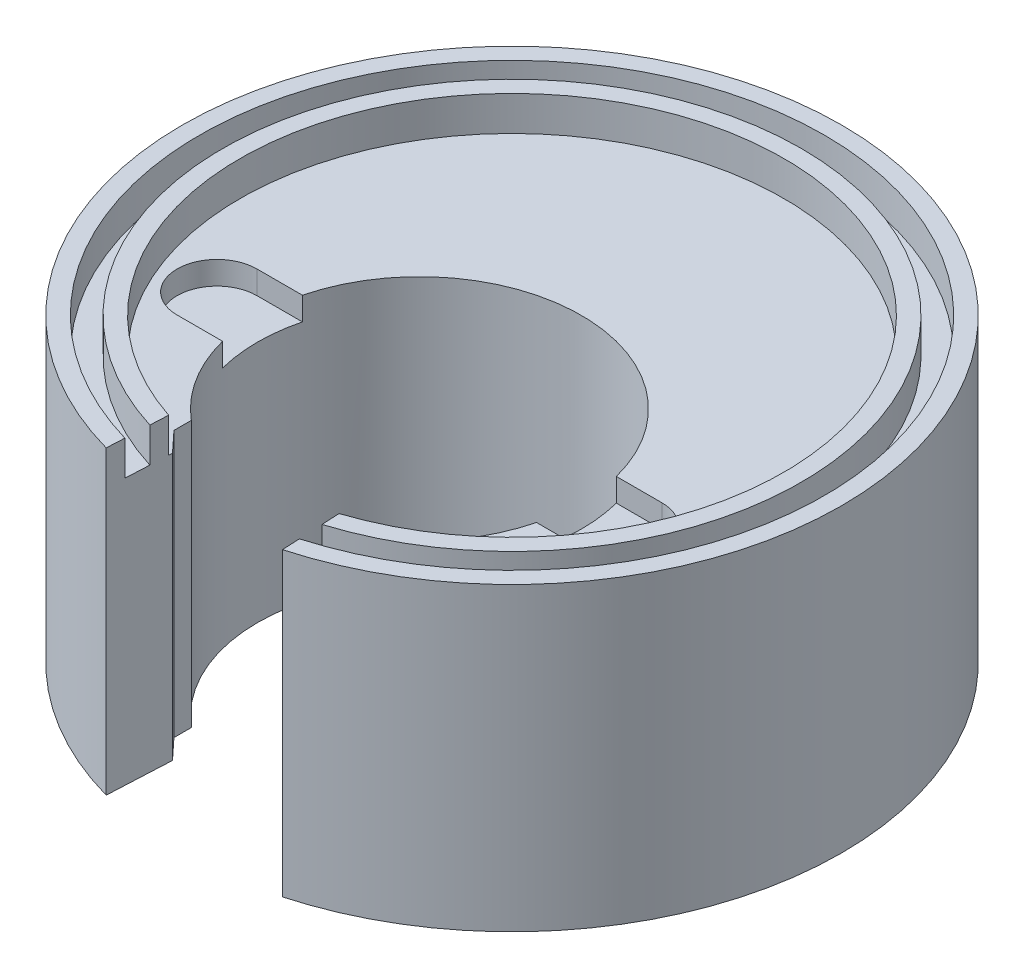
SolidWorks part; units mm, degrees
material "Custom Plastic"
ref_plane "Front Plane" through (0, 0, 0) normal (0, 0, 1) x (1, 0, 0)
ref_plane "Top Plane" through (0, 0, 0) normal (0, 1, 0) x (1, 0, 0)
ref_plane "Right Plane" through (0, 0, 0) normal (1, 0, 0) x (0, 0, -1)
sketch "Sketch1" plane through (0, 0, 0) normal (0, 1, 0) x (1, 0, 0)
  circle A0 centre (0, 0) radius 28.5
  dimension "D1" = 57
extrude "Boss-Extrude1" add sketch "Sketch1" along normal blind 3
sketch "Sketch2" plane through (0, 3, 0) normal (0, 1, 0) x (1, 0, 0)
  line L11 (0, 0) -> (0, -8) construction
  line L16 (-9, -18.7238) -> (-9, -20.2238)
  line L17 (-9, -20.2238) -> (-7.35, -22)
  line L18 (-7.35, -22) -> (-7.6173, -27.4632)
  line L20 (7.6173, -27.4632) -> (7.35, -22)
  line L21 (7.35, -22) -> (9, -20.2238)
  line L22 (9, -20.2238) -> (9, -18.7238)
  circle A9 centre (0, 0) radius 28.5 construction
  arc A10 (9, -18.7238) -> (13.5683, -11.45) centre (0, -8) ccw
  arc A12 (13.5683, -4.55) -> (-13.5683, -4.55) centre (0, -8) ccw
  arc A14 (-13.5683, -11.45) -> (-9, -18.7238) centre (0, -8) ccw
  arc A16 (-13.5683, -4.55) -> (-13.5683, -11.45) centre (0, -8) ccw
  arc A17 (13.5683, -4.55) -> (13.5683, -11.45) centre (0, -8) cw
  circle A18 centre (0, 0) radius 28.5
  circle M19 centre (0, 0) radius 28.5
  dimension "D2" = 57
  dimension "D1" = 8
extrude "Boss-Extrude4" add sketch "Sketch2" along normal blind 20 contours A12 A17 A10 L22 L21 L20 L18 L17 L16 A14 A16 M19 region at (-9.7988, 3, 19.4738)
sketch "Sketch5" plane through (0, 23, 0) normal (0, 1, 0) x (1, 0, 0)
  circle A0 centre (0, 0) radius 28.5
  circle A1 centre (0, 0) radius 23.5
  circle A2 centre (0, 0) radius 25
  circle A3 centre (0, 0) radius 27
  line M3 (9, -20.2238) -> (7.35, -22)
  line M4 (7.35, -22) -> (7.6173, -27.4632)
  arc M5 (7.6173, -27.4632) -> (-7.6173, -27.4632) centre (0, 0) ccw
  line M6 (-7.6173, -27.4632) -> (-7.35, -22)
  line M7 (-7.35, -22) -> (-9, -20.2238)
  dimension "D1" = 47
  dimension "D2" = 57
  dimension "D3" = 50
  dimension "D4" = 54
extrude "Boss-Extrude7" add sketch "Sketch5" along normal blind 3 contours A2 A1 M4 M6 M7 M3 | A3 M4 M5 M6 region at (22.0505, 23, 16.767) region at (-14.4007, 23, -19.5743)
sketch "Sketch6" plane through (0, 23, 0) normal (0, 1, 0) x (1, 0, 0)
  line L0 (13.5683, -11.45) -> (17.5, -11.45)
  line L1 (17.5, -4.55) -> (13.5683, -4.55)
  line L2 (-13.5683, -4.55) -> (-17.5, -4.55)
  line L3 (-17.5, -11.45) -> (-13.5683, -11.45)
  line L4 (-9, -18.7238) -> (-9, -20.2238)
  line L5 (-9, -20.2238) -> (-7.35, -22)
  line L6 (-7.35, -22) -> (-7.35, -25)
  line L7 (-7.35, -25) -> (7.35, -25)
  line L8 (7.35, -25) -> (7.35, -22)
  line L9 (7.35, -22) -> (9, -20.2238)
  line L10 (9, -20.2238) -> (9, -18.7238)
  arc A0 (9, -18.7238) -> (13.5683, -11.45) centre (0, -8) ccw
  arc A1 (17.5, -11.45) -> (17.5, -4.55) centre (17.5, -8) ccw
  arc A2 (13.5683, -4.55) -> (-13.5683, -4.55) centre (0, -8) ccw
  arc A3 (-17.5, -4.55) -> (-17.5, -11.45) centre (-17.5, -8) ccw
  arc A4 (-13.5683, -11.45) -> (-9, -18.7238) centre (0, -8) ccw
extrude "Cut-Extrude1" cut sketch "Sketch6" against normal blind 2
sketch "Sketch7" plane through (0, 3, 0) normal (0, 1, 0) x (1, 0, 0)
  line L6 (-9, -20.2238) -> (-7.35, -22)
  line L7 (-7.35, -22) -> (-7.6173, -27.4632)
  line L8 (7.6173, -27.4632) -> (7.35, -22)
  line L9 (7.35, -22) -> (9, -20.2238)
  line L10 (9, -20.2238) -> (9, -18.7238)
  line L11 (-9, -18.7238) -> (-9, -20.2238)
  line L12 (-9, -20.2238) -> (-7.35, -22)
  line L13 (-7.35, -22) -> (-7.6173, -27.4632)
  line L14 (7.6173, -27.4632) -> (7.35, -22)
  line L15 (7.35, -22) -> (9, -20.2238)
  line L16 (9, -20.2238) -> (9, -18.7238)
  line L17 (-9, -18.7238) -> (-9, -20.2238)
  arc A2 (-7.6173, -27.4632) -> (7.6173, -27.4632) centre (0, 0) ccw
  arc A3 (9, -18.7238) -> (-9, -18.7238) centre (0, -8) ccw
  arc A4 (-7.6173, -27.4632) -> (7.6173, -27.4632) centre (0, 0) ccw
  arc A5 (9, -18.7238) -> (-9, -18.7238) centre (0, -8) ccw
  dimension "D1" = 0
extrude "Cut-Extrude5" cut sketch "Sketch7" against normal blind 4
